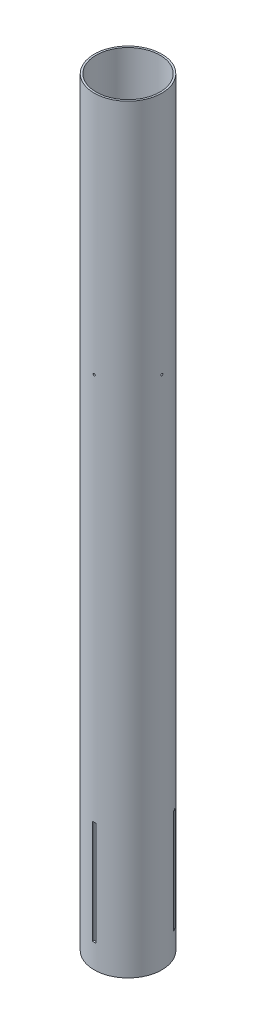
SolidWorks part; units mm, degrees
material "Hexcel AS4C (3000 Filaments)"
ref_plane "Front Plane" through (0, 0, 0) normal (0, 0, 1) x (1, 0, 0)
ref_plane "Top Plane" through (0, 0, 0) normal (0, 1, 0) x (1, 0, 0)
ref_plane "Right Plane" through (0, 0, 0) normal (1, 0, 0) x (0, 0, -1)
sketch "Sketch1" plane through (0, 0, 0) normal (0, 1, 0) x (1, 0, 0)
  circle A0 centre (0, 0) radius 50.8
  dimension "D1" = 101.6
extrude "Body Tube Extrusion" add sketch "Sketch1" along normal blind 1206.5 thin thin type one direction wall 2.921
ref_plane "Plane1" through (0, 0, 53.721) normal (0, 0, 1) x (1, 0, 0)
sketch "Sketch2" plane through (0, 0, 53.721) normal (0, 0, 1) x (1, 0, 0)
  line L0 (0, 1206.5) -> (0, 0) construction
  line L1 (50.8, 1206.5) -> (-50.8, 1206.5) construction
  line L2 (-53.721, 0) -> (53.721, 0) construction
  circle A0 centre (0, 819.15) radius 1.6383
  dimension "D1" = 3.2766
  dimension "D2" = 819.15
extrude "Engine Block Hole" cut sketch "Sketch2" against normal up to next
pattern_circular "CirPattern1" count 4 over 360 about axis through (0, 1206.5, 0) along (0, -1, 0) of "Engine Block Hole"
sketch "Sketch3" plane through (0, 0, 53.721) normal (0, 0, 1) x (1, 0, 0)
  line L0 (0, 0) -> (0, 38.1) construction
  line L1 (-50.8, 0) -> (50.8, 0) construction
  line L2 (0, 1206.5) -> (0, 0) construction
  line L4 (-2.667, 203.2) -> (2.667, 203.2)
  line L5 (-2.667, 203.2) -> (-2.667, 38.1)
  line L6 (-2.667, 38.1) -> (2.667, 38.1)
  line L7 (2.667, 203.2) -> (2.667, 38.1)
  point P10 (0, 38.1)
  dimension "D1" = 165.1
  dimension "D2" = 5.334
  dimension "D3" = 38.1
extrude "Fin Tab Slots" cut sketch "Sketch3" against normal blind 2.54
pattern_circular "CirPattern2" count 3 over 360 about axis through (0, 1206.5, 0) along (0, -1, 0) of "Fin Tab Slots" reverse direction yes
